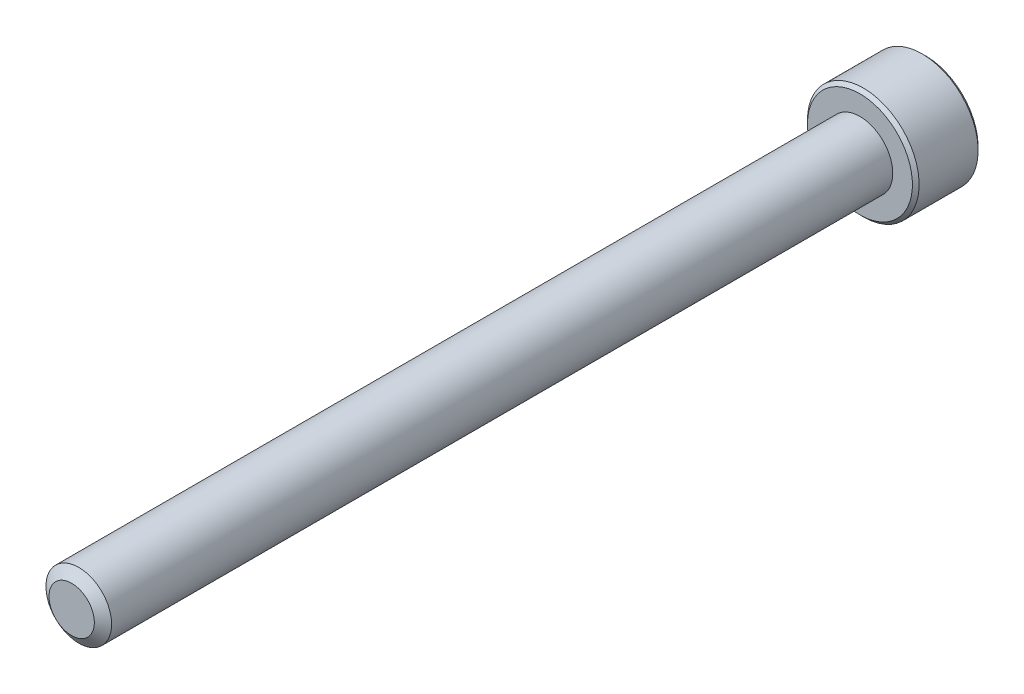
SolidWorks part; units mm, degrees
material "Alloy Steel"
ref_plane "Front Plane" through (0, 0, 0) normal (0, 0, 1) x (1, 0, 0)
ref_plane "Top Plane" through (0, 0, 0) normal (0, 1, 0) x (1, 0, 0)
ref_plane "Right Plane" through (0, 0, 0) normal (1, 0, 0) x (0, 0, -1)
sketch "Sketch1" plane through (0, 0, 0) normal (0, 0, 1) x (1, 0, 0)
  circle A0 centre (0, 0) radius 2.5
  dimension "OD" = 5
extrude "Extrude1" add sketch "Sketch1" against normal blind 60
sketch "Sketch2" plane through (0, 0, 0) normal (0, 0, 1) x (1, 0, 0)
  circle A0 centre (0, 0) radius 2.5 construction
  circle A1 centre (0, 0) radius 2.5
curve "Helix/Spiral1" [suppressed] pitch 0.8 height 60.8 turns 76 parameters "pitch"=0.8
sketch "Sketch3" plane through (0, 0, 0) normal (1, 0, 0) x (0, 0, -1)
  line L0 (-0.7, 2.5) -> (-0.4, 1.9804)
  line L1 (-0.4, 1.9804) -> (-0.3, 1.9804)
  line L2 (-0.3, 1.9804) -> (0, 2.5)
  line L3 (-0.7, 2.5) -> (0, 2.5)
  line L4 (-0.35, 2.5) -> (-0.35, 1.9804) construction
  line L5 (-0.55, 2.2402) -> (-0.15, 2.2402) construction
  line L6 (0, 2.5) -> (0, -2.5) construction
  line L7 (0, -2.5) -> (60, -2.5) construction
  point P11 (3.6, -2.5)
  dimension "D1" = 0.1
  dimension "D2" = 0.4
  dimension "D3" = 60
  dimension "D4" = 3.6
sweep "Cut-Sweep1" [suppressed] cut profiles "Sketch3" path "Helix/Spiral1"
sketch "Sketch4" plane through (0, 0, 0) normal (1, 0, 0) x (0, 0, -1)
  line L0 (0.5417, 2.5) -> (0, 1.7264)
  line L1 (0, 1.7264) -> (0, 2.5)
  line L2 (0.5417, 2.5) -> (0, 2.5)
  line L3 (-0.7, 2.5) -> (0, 2.5) construction
  line L4 (0, 0) -> (7.0209, 0) construction
  dimension "D1" = 55
  dimension "D2" = 0.254
revolve "Cut-Revolve1" cut sketch "Sketch4" angle 360 about L4
sketch "Sketch5" [suppressed] plane through (0, 0, 0) normal (1, 0, 0) x (0, 0, -1)
  line L0 (60, -1.991) -> (60, 1.7838) construction
  line L1 (60, 2.5) -> (22.1202, 2.5)
  line L2 (60, 2.5) -> (60, 0)
  line L3 (60, 0) -> (22, 0)
  line L4 (22, 2.1698) -> (22, 0)
  line L5 (22.1202, 2.5) -> (22, 2.1698)
  line L6 (0, 0) -> (9.9695, 0) construction
  point P3 (22, 2.5)
  point P10 (22, 2.5)
  dimension "D1" = 0.3302
  dimension "Thread min" = 22
  dimension "D3" = 20
revolve "partially thread" [suppressed] add sketch "Sketch5" angle 360 about L6
sketch "Sketch6" plane through (0, 0, -60) normal (0, 0, -1) x (-1, 0, 0)
  circle A0 centre (0, 0) radius 4.25
  dimension "head dia" = 8.5
extrude "Extrude2" add sketch "Sketch6" along normal blind 5
sketch "Sketch7" plane through (0, 0, -65) normal (0, 0, -1) x (-1, 0, 0)
  line L1 (0, 2.3094) -> (-2, 1.1547)
  line L2 (-2, 1.1547) -> (-2, -1.1547)
  line L3 (-2, -1.1547) -> (0, -2.3094)
  line L4 (0, -2.3094) -> (2, -1.1547)
  line L5 (2, -1.1547) -> (2, 1.1547)
  line L6 (2, 1.1547) -> (0, 2.3094)
  circle A0 centre (0, 0) radius 2 construction
  dimension "hex dia" = 4
extrude "Cut-Extrude1" cut sketch "Sketch7" against normal blind 3
sketch "Sketch8" plane through (0, 0, -65) normal (0, 0, -1) x (-1, 0, 0)
  circle A0 centre (0, 0) radius 2.3094
extrude "Cut-Extrude2" cut sketch "Sketch8" against normal through all draft 45
chamfer "Chamfer1" distance 0.255 angle 45 2 edges at (-4.25, 0, -65) (-4.25, 0, -60)
sketch "Sketch9" plane through (0, 0, 0) normal (1, 0, 0) x (0, 0, -1)
  line L0 (0, 2.5) -> (0, -2.5) construction
  line L1 (4.4, 2.5) -> (4.4, -2.5) construction
  dimension "D1" = 4.4
sketch "Sketch10" plane through (0, 0, 0) normal (1, 0, 0) x (0, 0, -1)
  line L0 (60, 2.5) -> (60, 0)
  line L1 (60, 2.5) -> (59.8, 2.5)
  line L2 (59.8, 2.5) -> (58.7645, 0)
  line L3 (60, 0) -> (58.7645, 0)
  line L4 (60, 3.995) -> (60, -3.995) construction
  dimension "D1" = 22.5
  dimension "D2" = 0.2
revolve "Revolve1" add sketch "Sketch10" angle 360 about L3
equation "\"D3@Helix/Spiral1\" = \"screw length@Extrude1\"+\"pitch@Helix/Spiral1\""
equation "\"D1@Sketch3\" = \"pitch@Helix/Spiral1\"*.125"
equation "\"D2@Sketch3\" = \"pitch@Helix/Spiral1\"*.5"
equation "\"D1@Cut-Extrude1\" = \"hex dia@Sketch7\"*.75"
equation "\"D1@Chamfer1\" = \"head dia@Sketch6\"*.03"
equation "\"D1@Sketch9\" = \"pitch@Helix/Spiral1\"*5.5"
equation "\"D2@Sketch10\" = \"pitch@Helix/Spiral1\"*.25"
equation "\"D4@Sketch3\" = \"pitch@Helix/Spiral1\"*4.50"
